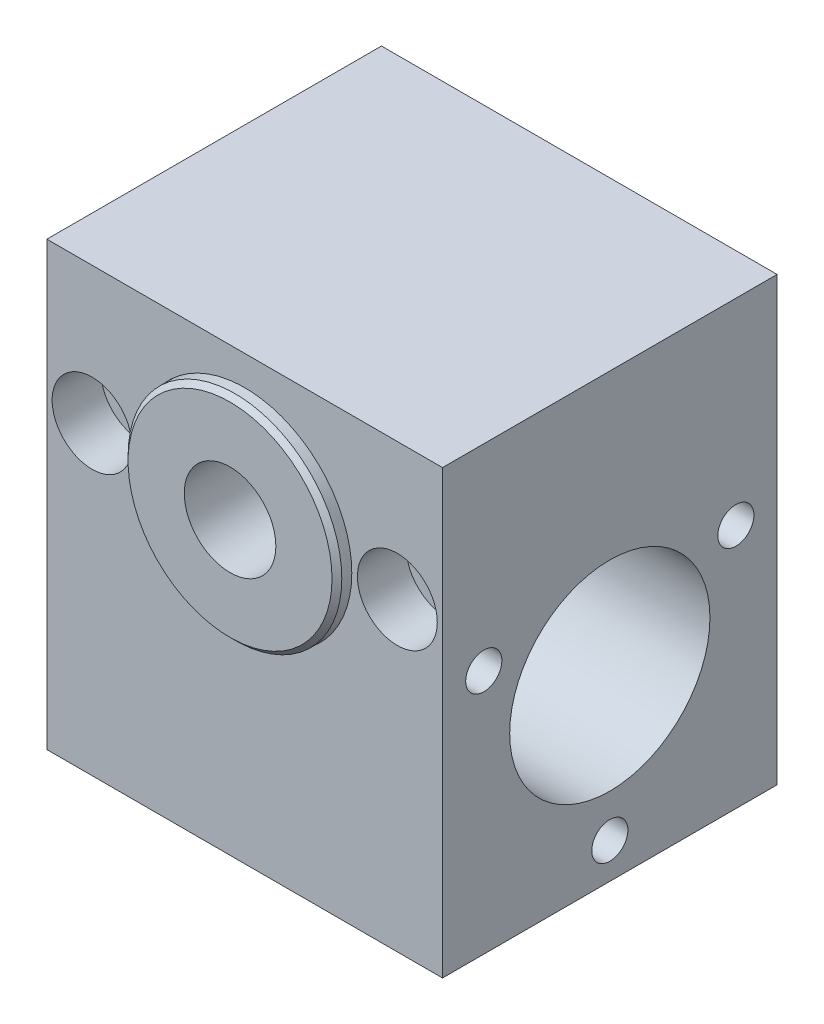
SolidWorks part; units mm, degrees
material "6061-T6 (SS)"
ref_plane "Front Plane" through (0, 0, 0) normal (0, 0, 1) x (1, 0, 0)
ref_plane "Top Plane" through (0, 0, 0) normal (0, 1, 0) x (1, 0, 0)
ref_plane "Right Plane" through (0, 0, 0) normal (1, 0, 0) x (0, 0, -1)
sketch "Sketch1" plane through (0, 0, 0) normal (1, 0, 0) x (0, 0, -1)
  line L0 (-17.399, 0) -> (17.399, 0)
  line L1 (17.399, 0) -> (17.399, 45.974)
  line L2 (17.399, 45.974) -> (-17.399, 45.974)
  line L3 (-17.399, 45.974) -> (-17.399, 0)
  circle A0 centre (0, 18.542) radius 10.414
extrude "Boss-Extrude1" add sketch "Sketch1" against normal blind 20.574 and the other way blind 20.574
ref_plane "Plane1" through (15.875, 0, 0) normal (1, 0, 0) x (0, 0, -1)
sketch "Sketch2" plane through (15.875, 0, 0) normal (1, 0, 0) x (0, 0, -1)
  line L0 (-17.399, 31.75) -> (-17.399, 35.9029)
  line L1 (-17.399, 35.9029) -> (-12.319, 35.9029)
  line L2 (-12.319, 35.9029) -> (-12.319, 34.3297)
  line L3 (-12.319, 34.3297) -> (12.319, 34.3297)
  line L4 (12.319, 34.3297) -> (12.319, 35.9029)
  line L5 (12.319, 35.9029) -> (17.399, 35.9029)
  line L6 (17.399, 35.9029) -> (17.399, 31.75)
  line L7 (17.399, 31.75) -> (-17.399, 31.75)
  line L8 (17.399, 31.75) -> (-17.399, 31.75) construction
revolve "Cut-Revolve1" cut sketch "Sketch2" angle 360 about L8 reverse direction yes
ref_plane "Plane2" through (-15.875, 0, 0) normal (1, 0, 0) x (0, 0, -1)
sketch "Sketch3" plane through (-15.875, 0, 0) normal (1, 0, 0) x (0, 0, -1)
  line L0 (-17.399, 31.75) -> (-17.399, 35.9029)
  line L1 (-17.399, 35.9029) -> (-12.319, 35.9029)
  line L2 (-12.319, 35.9029) -> (-12.319, 34.3297)
  line L3 (-12.319, 34.3297) -> (12.319, 34.3297)
  line L4 (12.319, 34.3297) -> (12.319, 35.9029)
  line L5 (12.319, 35.9029) -> (17.399, 35.9029)
  line L6 (17.399, 35.9029) -> (17.399, 31.75)
  line L7 (17.399, 31.75) -> (-17.399, 31.75)
  line L8 (17.399, 31.75) -> (-17.399, 31.75) construction
revolve "Cut-Revolve2" cut sketch "Sketch3" angle 360 about L8 reverse direction yes
ref_plane "Plane3" through (0, 0, 12.7) normal (0, 0, 1) x (1, 0, 0)
hole_wizard "Hole1" positions "Sketch5" profile "Sketch4" legacy
sketch "Sketch5" plane through (0, 0, 0) normal (0, -1, 0) x (-1, 0, 0)
  point P0 (0, -12.7)
sketch "Sketch4" plane through (0, 0, 12.7) normal (1, 0, 0) x (0, 0, -1)
  line L0 (0, 0) -> (0, 12.7277)
  line L1 (0, 12.7277) -> (1.9837, 11.5824)
  line L2 (1.9837, 11.5824) -> (1.9837, 0.4293)
  line L3 (1.9837, 0.4293) -> (2.413, 0)
  line L4 (2.413, 0) -> (0, 0)
  line L5 (0, -14.3089) -> (0, 102.4216) construction
  line L6 (0, 12.7277) -> (-1.9837, 11.5824) construction
  line L7 (-1.9837, 0.4293) -> (-2.413, 0) construction
  dimension "Diameter" = 3.9675
  dimension "Depth" = 11.5824
  dimension "C-Sink Diameter" = 4.826
  dimension "C-Sink Angle" = 90
  dimension "Drill Angle" = 120
cosmetic thread "Cosmetic Thread1" parameters "D1"=9.652, "D2"=4.826
ref_plane "Plane4" through (0, 0, -12.7) normal (0, 0, 1) x (1, 0, 0)
hole_wizard "Hole2" positions "Sketch7" profile "Sketch6" legacy
sketch "Sketch7" plane through (0, 0, 0) normal (0, -1, 0) x (-1, 0, 0)
  point P0 (0, 12.7)
sketch "Sketch6" plane through (0, 0, -12.7) normal (1, 0, 0) x (0, 0, -1)
  line L0 (0, 0) -> (0, 12.7277)
  line L1 (0, 12.7277) -> (1.9837, 11.5824)
  line L2 (1.9837, 11.5824) -> (1.9837, 0.4293)
  line L3 (1.9837, 0.4293) -> (2.413, 0)
  line L4 (2.413, 0) -> (0, 0)
  line L5 (0, -14.3089) -> (0, 102.4216) construction
  line L6 (0, 12.7277) -> (-1.9837, 11.5824) construction
  line L7 (-1.9837, 0.4293) -> (-2.413, 0) construction
  dimension "Diameter" = 3.9675
  dimension "Depth" = 11.5824
  dimension "C-Sink Diameter" = 4.826
  dimension "C-Sink Angle" = 90
  dimension "Drill Angle" = 120
cosmetic thread "Cosmetic Thread2" parameters "D1"=9.652, "D2"=4.826
hole_wizard "Hole3" positions "Sketch9" profile "Sketch8" legacy
sketch "Sketch9" plane through (0, 0, 17.399) normal (0, 0, 1) x (1, 0, 0)
  point P0 (0, 31.75)
sketch "Sketch8" plane through (0, 31.75, 17.399) normal (1, 0, 0) x (0, -1, 0)
  line L0 (0, 0) -> (0, 34.798)
  line L1 (0, 34.798) -> (4.7625, 34.798)
  line L2 (4.7625, 34.798) -> (4.7625, 24.638)
  line L3 (4.7625, 24.638) -> (11.1379, 24.638)
  line L4 (11.1379, 24.638) -> (11.1379, 0)
  line L5 (11.1379, 0) -> (0, 0)
  line L6 (0, 110) -> (0, -10) construction
  dimension "Diameter" = 9.525
  dimension "Depth" = 34.798
  dimension "C-Bore Diameter" = 22.2758
  dimension "C-Bore Depth" = 24.638
ref_plane "Plane5" through (20.574, 0, 0) normal (1, 0, 0) x (0, 0, -1)
ref_plane "Plane6" through (-20.574, 0, 0) normal (1, 0, 0) x (0, 0, -1)
ref_plane "Plane7" through (0, 0, 18.923) normal (0, 0, 1) x (1, 0, 0)
ref_plane "Plane8" through (0, 0, 44.323) normal (0, 0, 1) x (1, 0, 0)
ref_plane "Plane9" through (0, 0, -44.323) normal (0, 0, 1) x (1, 0, 0)
ref_plane "Plane10" through (0, 0, -17.399) normal (0, 0, 1) x (1, 0, 0)
ref_plane "Plane11" through (0, 0, -18.923) normal (0, 0, 1) x (1, 0, 0)
ref_plane "Plane12" through (0, 0, -17.399) normal (0, 0, 1) x (1, 0, 0)
sketch "Sketch10" plane through (0, 0, 0) normal (1, 0, 0) x (0, 0, -1)
  line L0 (-18.923, 42.3545) -> (-18.923, 36.5125)
  line L1 (-18.923, 36.5125) -> (7.239, 36.5125)
  line L2 (7.239, 36.5125) -> (7.239, 42.8625)
  line L3 (7.239, 42.8625) -> (-18.415, 42.8625)
  line L4 (-18.415, 42.8625) -> (-18.923, 42.3545)
  line L5 (7.239, 31.75) -> (-18.923, 31.75) construction
revolve "Revolve1" add sketch "Sketch10" angle 360 about L5 reverse direction yes
ref_plane "Plane13" through (20.574, 0, 0) normal (1, 0, 0) x (0, 0, -1)
hole_wizard "Hole4" positions "Sketch12" profile "Sketch11" legacy
sketch "Sketch12" plane through (20.574, 0, 0) normal (1, 0, 0) x (0, 0, -1)
  point P0 (13.1085, 25.5119)
sketch "Sketch11" plane through (20.574, 25.5119, -13.1085) normal (0, 1, 0) x (0, 0, -1)
  line L0 (0, 0) -> (0, 7.5184)
  line L1 (0, 7.5184) -> (1.8796, 7.5184)
  line L2 (1.8796, 7.5184) -> (1.8796, 0)
  line L3 (1.8796, 0) -> (0, 0)
  line L4 (0, 110) -> (0, -10) construction
  dimension "Diameter" = 3.7592
  dimension "Depth" = 7.5184
sketch "Sketch13" plane through (20.574, 0, 0) normal (1, 0, 0) x (0, 0, -1)
  line L0 (13.1085, 25.5119) -> (-13.1085, 25.5119)
  line L1 (13.1085, 25.5119) -> (0, 3.6957)
pattern_linear "LPattern2" count 2 spacing 26.217 along (0, 0, 1) count 2 spacing 25.4515 along (0, -0.8572, 0.515) skipping (1, 1) of "Hole4"
ref_plane "Plane14" through (-20.574, 0, 0) normal (1, 0, 0) x (0, 0, -1)
hole_wizard "Hole5" positions "Sketch15" profile "Sketch14" legacy
sketch "Sketch15" plane through (-20.574, 0, 0) normal (-1, 0, 0) x (0, 0, 1)
  point P0 (-13.1085, 25.5119)
sketch "Sketch14" plane through (-20.574, 25.5119, -13.1085) normal (0, 1, 0) x (0, 0, 1)
  line L0 (0, 0) -> (0, 7.5184)
  line L1 (0, 7.5184) -> (1.8796, 7.5184)
  line L2 (1.8796, 7.5184) -> (1.8796, 0)
  line L3 (1.8796, 0) -> (0, 0)
  line L4 (0, 110) -> (0, -10) construction
  dimension "Diameter" = 3.7592
  dimension "Depth" = 7.5184
sketch "Sketch16" plane through (-20.574, 0, 0) normal (1, 0, 0) x (0, 0, -1)
  line L0 (13.1085, 25.5119) -> (-13.1085, 25.5119)
  line L1 (13.1085, 25.5119) -> (0, 3.6957)
pattern_linear "LPattern4" count 2 spacing 26.217 along (0, 0, 1) count 2 spacing 25.4515 along (0, -0.8572, 0.515) skipping (1, 1) of "Hole5"
ref_plane "Plane15" through (0, 31.75, 0) normal (0, 1, 0) x (1, 0, 0)
ref_plane "a1 XY" through (0, 0, 0) normal (0, 0, 1) x (1, 0, 0)
ref_plane "a1 XZ" through (0, 45.974, 0) normal (0, -1, 0) x (-1, 0, 0)
ref_plane "a1 YZ" through (-20.574, 0, 0) normal (1, 0, 0) x (0, 0, -1)
ref_axis "a1 X" through (-80.9, 45.974, 0) along (1, 0, 0)
ref_axis "a1 Y" through (-20.574, -50, 0) along (0, 1, 0)
ref_axis "a1 Z" through (-20.574, 45.974, 80.9) along (0, 0, -1)
sketch3d "a1"
  point P0 (-20.574, 45.974, 0)
ref_plane "a2 XY" through (0, 0, 0) normal (0, 0, 1) x (1, 0, 0)
ref_plane "a2 XZ" through (0, 45.974, 0) normal (0, -1, 0) x (-1, 0, 0)
ref_plane "a2 YZ" through (20.574, 0, 0) normal (1, 0, 0) x (0, 0, -1)
ref_axis "a2 X" through (-80.9, 45.974, 0) along (1, 0, 0)
ref_axis "a2 Y" through (20.574, -50, 0) along (0, 1, 0)
ref_axis "a2 Z" through (20.574, 45.974, 80.9) along (0, 0, -1)
sketch3d "a2"
  point P0 (20.574, 45.974, 0)
ref_plane "ab XY" through (0, 0, 0) normal (1, 0, 0) x (0, 0, -1)
ref_plane "ab XZ" through (0, 18.542, 0) normal (0, -1, 0) x (-1, 0, 0)
ref_plane "ab YZ" through (0, 0, 0) normal (0, 0, -1) x (-1, 0, 0)
ref_axis "ab X" through (0, 18.542, 80.9) along (0, 0, -1)
ref_axis "ab Y" through (0, -50, 0) along (0, 1, 0)
ref_axis "ab Z" through (80.9, 18.542, 0) along (-1, 0, 0)
sketch3d "ab"
  point P0 (0, 18.542, 0)
ref_plane "b1 XY" through (0, 0, 0) normal (0, 0, 1) x (1, 0, 0)
ref_plane "b1 XZ" through (0, 31.75, 0) normal (0, -1, 0) x (-1, 0, 0)
ref_plane "b1 YZ" through (-15.875, 0, 0) normal (1, 0, 0) x (0, 0, -1)
ref_axis "b1 X" through (-80.9, 31.75, 0) along (1, 0, 0)
ref_axis "b1 Y" through (-15.875, -50, 0) along (0, 1, 0)
ref_axis "b1 Z" through (-15.875, 31.75, 80.9) along (0, 0, -1)
sketch3d "b1"
  point P0 (-15.875, 31.75, 0)
ref_plane "b2 XY" through (0, 0, 0) normal (0, 0, 1) x (1, 0, 0)
ref_plane "b2 XZ" through (0, 31.75, 0) normal (0, -1, 0) x (-1, 0, 0)
ref_plane "b2 YZ" through (15.875, 0, 0) normal (1, 0, 0) x (0, 0, -1)
ref_axis "b2 X" through (-80.9, 31.75, 0) along (1, 0, 0)
ref_axis "b2 Y" through (15.875, -50, 0) along (0, 1, 0)
ref_axis "b2 Z" through (15.875, 31.75, 80.9) along (0, 0, -1)
sketch3d "b2"
  point P0 (15.875, 31.75, 0)
ref_plane "body a single XY" through (-20.574, 0, 0) normal (1, 0, 0) x (0, 0, -1)
ref_plane "body a single XZ" through (0, 18.542, 0) normal (0, -1, 0) x (-1, 0, 0)
ref_plane "body a single YZ" through (0, 0, 0) normal (0, 0, -1) x (-1, 0, 0)
ref_axis "body a single X" through (-20.574, 18.542, 80.9) along (0, 0, -1)
ref_axis "body a single Y" through (-20.574, -50, 0) along (0, 1, 0)
ref_axis "body a single Z" through (80.9, 18.542, 0) along (-1, 0, 0)
sketch3d "body a single"
  point P0 (-20.574, 18.542, 0)
ref_plane "body b single XY" through (20.574, 0, 0) normal (1, 0, 0) x (0, 0, -1)
ref_plane "body b single XZ" through (0, 18.542, 0) normal (0, -1, 0) x (-1, 0, 0)
ref_plane "body b single YZ" through (0, 0, 0) normal (0, 0, -1) x (-1, 0, 0)
ref_axis "body b single X" through (20.574, 18.542, 80.9) along (0, 0, -1)
ref_axis "body b single Y" through (20.574, -50, 0) along (0, 1, 0)
ref_axis "body b single Z" through (80.9, 18.542, 0) along (-1, 0, 0)
sketch3d "body b single"
  point P0 (20.574, 18.542, 0)
ref_plane "c1 XY" through (0, 0, 0) normal (0, 0, 1) x (1, 0, 0)
ref_plane "c1 XZ" through (0, 31.75, 0) normal (0, -1, 0) x (-1, 0, 0)
ref_plane "c1 YZ" through (-15.875, 0, 0) normal (1, 0, 0) x (0, 0, -1)
ref_axis "c1 X" through (-80.9, 31.75, 0) along (1, 0, 0)
ref_axis "c1 Y" through (-15.875, -50, 0) along (0, 1, 0)
ref_axis "c1 Z" through (-15.875, 31.75, 80.9) along (0, 0, -1)
sketch3d "c1"
  point P0 (-15.875, 31.75, 0)
ref_plane "c2 XY" through (0, 0, 0) normal (0, 0, 1) x (1, 0, 0)
ref_plane "c2 XZ" through (0, 31.75, 0) normal (0, -1, 0) x (-1, 0, 0)
ref_plane "c2 YZ" through (0, 0, 0) normal (1, 0, 0) x (0, 0, -1)
ref_axis "c2 X" through (-80.9, 31.75, 0) along (1, 0, 0)
ref_axis "c2 Y" through (0, -50, 0) along (0, 1, 0)
ref_axis "c2 Z" through (0, 31.75, 80.9) along (0, 0, -1)
sketch3d "c2"
  point P0 (0, 31.75, 0)
ref_plane "e1 XY" through (0, 0, 0) normal (1, 0, 0) x (0, 0, -1)
ref_plane "e1 XZ" through (0, 45.974, 0) normal (0, -1, 0) x (-1, 0, 0)
ref_plane "e1 YZ" through (0, 0, 17.399) normal (0, 0, -1) x (-1, 0, 0)
ref_axis "e1 X" through (0, 45.974, 80.9) along (0, 0, -1)
ref_axis "e1 Y" through (0, -50, 17.399) along (0, 1, 0)
ref_axis "e1 Z" through (80.9, 45.974, 17.399) along (-1, 0, 0)
sketch3d "e1"
  point P0 (0, 45.974, 17.399)
ref_plane "e2 XY" through (0, 0, 0) normal (1, 0, 0) x (0, 0, -1)
ref_plane "e2 XZ" through (0, 0, 0) normal (0, -1, 0) x (-1, 0, 0)
ref_plane "e2 YZ" through (0, 0, 17.399) normal (0, 0, -1) x (-1, 0, 0)
ref_axis "e2 X" through (0, 0, 80.9) along (0, 0, -1)
ref_axis "e2 Y" through (0, -50, 17.399) along (0, 1, 0)
ref_axis "e2 Z" through (80.9, 0, 17.399) along (-1, 0, 0)
sketch3d "e2"
  point P0 (0, 0, 17.399)
ref_plane "f1 XY" through (0, 0, 0) normal (0, 0, 1) x (1, 0, 0)
ref_plane "f1 XZ" through (0, 31.75, 0) normal (0, -1, 0) x (-1, 0, 0)
ref_plane "f1 YZ" through (13.2953, 0, 0) normal (1, 0, 0) x (0, 0, -1)
ref_axis "f1 X" through (-80.9, 31.75, 0) along (1, 0, 0)
ref_axis "f1 Y" through (13.2953, -50, 0) along (0, 1, 0)
ref_axis "f1 Z" through (13.2953, 31.75, 80.9) along (0, 0, -1)
sketch3d "f1"
  point P0 (13.2953, 31.75, 0)
ref_plane "f2 XY" through (0, 0, 0) normal (0, 0, 1) x (1, 0, 0)
ref_plane "f2 XZ" through (0, 31.75, 0) normal (0, -1, 0) x (-1, 0, 0)
ref_plane "f2 YZ" through (18.4547, 0, 0) normal (1, 0, 0) x (0, 0, -1)
ref_axis "f2 X" through (-80.9, 31.75, 0) along (1, 0, 0)
ref_axis "f2 Y" through (18.4547, -50, 0) along (0, 1, 0)
ref_axis "f2 Z" through (18.4547, 31.75, 80.9) along (0, 0, -1)
sketch3d "f2"
  point P0 (18.4547, 31.75, 0)
ref_plane "g1 XY" through (0, 0, 0) normal (0, 0, 1) x (1, 0, 0)
ref_plane "g1 XZ" through (0, 31.75, 0) normal (0, -1, 0) x (-1, 0, 0)
ref_plane "g1 YZ" through (-11.1125, 0, 0) normal (1, 0, 0) x (0, 0, -1)
ref_axis "g1 X" through (-80.9, 31.75, 0) along (1, 0, 0)
ref_axis "g1 Y" through (-11.1125, -50, 0) along (0, 1, 0)
ref_axis "g1 Z" through (-11.1125, 31.75, 80.9) along (0, 0, -1)
sketch3d "g1"
  point P0 (-11.1125, 31.75, 0)
ref_plane "g1_1 XY" through (0, 31.75, 0) normal (0, 1, 0) x (1, 0, 0)
ref_plane "g1_1 XZ" through (0, 0, 17.399) normal (0, 0, 1) x (1, 0, 0)
ref_plane "g1_1 YZ" through (-11.1125, 0, 0) normal (1, 0, 0) x (0, 0, -1)
ref_axis "g1_1 X" through (-80.9, 31.75, 17.399) along (1, 0, 0)
ref_axis "g1_1 Y" through (-11.1125, 31.75, 50) along (0, 0, -1)
ref_axis "g1_1 Z" through (-11.1125, 50, 17.399) along (0, -1, 0)
sketch3d "g1_1"
  point P0 (-11.1125, 31.75, 17.399)
ref_plane "g1_2 XY" through (0, 31.75, 0) normal (0, 1, 0) x (1, 0, 0)
ref_plane "g1_2 XZ" through (0, 0, 17.399) normal (0, 0, 1) x (1, 0, 0)
ref_plane "g1_2 YZ" through (11.1125, 0, 0) normal (1, 0, 0) x (0, 0, -1)
ref_axis "g1_2 X" through (-80.9, 31.75, 17.399) along (1, 0, 0)
ref_axis "g1_2 Y" through (11.1125, 31.75, 50) along (0, 0, -1)
ref_axis "g1_2 Z" through (11.1125, 50, 17.399) along (0, -1, 0)
sketch3d "g1_2"
  point P0 (11.1125, 31.75, 17.399)
ref_plane "g2 XY" through (0, 0, 0) normal (0, 0, 1) x (1, 0, 0)
ref_plane "g2 XZ" through (0, 31.75, 0) normal (0, -1, 0) x (-1, 0, 0)
ref_plane "g2 YZ" through (11.1125, 0, 0) normal (1, 0, 0) x (0, 0, -1)
ref_axis "g2 X" through (-80.9, 31.75, 0) along (1, 0, 0)
ref_axis "g2 Y" through (11.1125, -50, 0) along (0, 1, 0)
ref_axis "g2 Z" through (11.1125, 31.75, 80.9) along (0, 0, -1)
sketch3d "g2"
  point P0 (11.1125, 31.75, 0)
ref_plane "h1 XY" through (0, 0, 0) normal (1, 0, 0) x (0, 0, -1)
ref_plane "h1 XZ" through (0, 36.5125, 0) normal (0, -1, 0) x (-1, 0, 0)
ref_plane "h1 YZ" through (0, 0, 44.323) normal (0, 0, -1) x (-1, 0, 0)
ref_axis "h1 X" through (0, 36.5125, 80.9) along (0, 0, -1)
ref_axis "h1 Y" through (0, -50, 44.323) along (0, 1, 0)
ref_axis "h1 Z" through (80.9, 36.5125, 44.323) along (-1, 0, 0)
sketch3d "h1"
  point P0 (0, 36.5125, 44.323)
ref_plane "h2 XY" through (0, 0, 0) normal (1, 0, 0) x (0, 0, -1)
ref_plane "h2 XZ" through (0, 26.9875, 0) normal (0, -1, 0) x (-1, 0, 0)
ref_plane "h2 YZ" through (0, 0, 44.323) normal (0, 0, -1) x (-1, 0, 0)
ref_axis "h2 X" through (0, 26.9875, 80.9) along (0, 0, -1)
ref_axis "h2 Y" through (0, -50, 44.323) along (0, 1, 0)
ref_axis "h2 Z" through (80.9, 26.9875, 44.323) along (-1, 0, 0)
sketch3d "h2"
  point P0 (0, 26.9875, 44.323)
ref_plane "l_ab XY" through (0, 0, 0) normal (0, 0, 1) x (1, 0, 0)
ref_plane "l_ab XZ" through (0, 0, 0) normal (0, -1, 0) x (-1, 0, 0)
ref_plane "l_ab YZ" through (0, 0, 0) normal (1, 0, 0) x (0, 0, -1)
ref_axis "l_ab X" through (-80.9, 0, 0) along (1, 0, 0)
ref_axis "l_ab Y" through (0, -50, 0) along (0, 1, 0)
ref_axis "l_ab Z" through (0, 0, 80.9) along (0, 0, -1)
sketch3d "l_ab"
  point P0 (0, 0, 0)
ref_plane "l_cd XY" through (0, 0, 0) normal (0, 0, 1) x (1, 0, 0)
ref_plane "l_cd XZ" through (0, 45.974, 0) normal (0, -1, 0) x (-1, 0, 0)
ref_plane "l_cd YZ" through (0, 0, 0) normal (1, 0, 0) x (0, 0, -1)
ref_axis "l_cd X" through (-80.9, 45.974, 0) along (1, 0, 0)
ref_axis "l_cd Y" through (0, -50, 0) along (0, 1, 0)
ref_axis "l_cd Z" through (0, 45.974, 80.9) along (0, 0, -1)
sketch3d "l_cd"
  point P0 (0, 45.974, 0)
ref_plane "m1 XY" through (0, 0, 0) normal (1, 0, 0) x (0, 0, -1)
ref_plane "m1 XZ" through (0, 45.974, 0) normal (0, -1, 0) x (-1, 0, 0)
ref_plane "m1 YZ" through (0, 0, 17.399) normal (0, 0, -1) x (-1, 0, 0)
ref_axis "m1 X" through (0, 45.974, 80.9) along (0, 0, -1)
ref_axis "m1 Y" through (0, -50, 17.399) along (0, 1, 0)
ref_axis "m1 Z" through (80.9, 45.974, 17.399) along (-1, 0, 0)
sketch3d "m1"
  point P0 (0, 45.974, 17.399)
ref_plane "m2 XY" through (0, 0, 0) normal (1, 0, 0) x (0, 0, -1)
ref_plane "m2 XZ" through (0, 45.974, 0) normal (0, -1, 0) x (-1, 0, 0)
ref_plane "m2 YZ" through (0, 0, -17.399) normal (0, 0, -1) x (-1, 0, 0)
ref_axis "m2 X" through (0, 45.974, 80.9) along (0, 0, -1)
ref_axis "m2 Y" through (0, -50, -17.399) along (0, 1, 0)
ref_axis "m2 Z" through (80.9, 45.974, -17.399) along (-1, 0, 0)
sketch3d "m2"
  point P0 (0, 45.974, -17.399)
ref_plane "n1 XY" through (0, 0, 0) normal (1, 0, 0) x (0, 0, -1)
ref_plane "n1 XZ" through (0, 31.75, 0) normal (0, -1, 0) x (-1, 0, 0)
ref_plane "n1 YZ" through (0, 0, 44.323) normal (0, 0, -1) x (-1, 0, 0)
ref_axis "n1 X" through (0, 31.75, 80.9) along (0, 0, -1)
ref_axis "n1 Y" through (0, -50, 44.323) along (0, 1, 0)
ref_axis "n1 Z" through (80.9, 31.75, 44.323) along (-1, 0, 0)
sketch3d "n1"
  point P0 (0, 31.75, 44.323)
ref_plane "n2 XY" through (0, 0, 0) normal (1, 0, 0) x (0, 0, -1)
ref_plane "n2 XZ" through (0, 45.974, 0) normal (0, -1, 0) x (-1, 0, 0)
ref_plane "n2 YZ" through (0, 0, 17.399) normal (0, 0, -1) x (-1, 0, 0)
ref_axis "n2 X" through (0, 45.974, 80.9) along (0, 0, -1)
ref_axis "n2 Y" through (0, -50, 17.399) along (0, 1, 0)
ref_axis "n2 Z" through (80.9, 45.974, 17.399) along (-1, 0, 0)
sketch3d "n2"
  point P0 (0, 45.974, 17.399)
ref_plane "o1 XY" through (0, 0, 0) normal (1, 0, 0) x (0, 0, -1)
ref_plane "o1 XZ" through (0, 45.974, 0) normal (0, -1, 0) x (-1, 0, 0)
ref_plane "o1 YZ" through (0, 0, 17.399) normal (0, 0, -1) x (-1, 0, 0)
ref_axis "o1 X" through (0, 45.974, 80.9) along (0, 0, -1)
ref_axis "o1 Y" through (0, -50, 17.399) along (0, 1, 0)
ref_axis "o1 Z" through (80.9, 45.974, 17.399) along (-1, 0, 0)
sketch3d "o1"
  point P0 (0, 45.974, 17.399)
ref_plane "o2 XY" through (0, 0, 0) normal (1, 0, 0) x (0, 0, -1)
ref_plane "o2 XZ" through (0, 45.974, 0) normal (0, -1, 0) x (-1, 0, 0)
ref_plane "o2 YZ" through (0, 0, 0) normal (0, 0, -1) x (-1, 0, 0)
ref_axis "o2 X" through (0, 45.974, 80.9) along (0, 0, -1)
ref_axis "o2 Y" through (0, -50, 0) along (0, 1, 0)
ref_axis "o2 Z" through (80.9, 45.974, 0) along (-1, 0, 0)
sketch3d "o2"
  point P0 (0, 45.974, 0)
ref_plane "p1 XY" through (0, 0, 0) normal (1, 0, 0) x (0, 0, -1)
ref_plane "p1 XZ" through (0, 31.75, 0) normal (0, -1, 0) x (-1, 0, 0)
ref_plane "p1 YZ" through (0, 0, 18.923) normal (0, 0, -1) x (-1, 0, 0)
ref_axis "p1 X" through (0, 31.75, 80.9) along (0, 0, -1)
ref_axis "p1 Y" through (0, -50, 18.923) along (0, 1, 0)
ref_axis "p1 Z" through (80.9, 31.75, 18.923) along (-1, 0, 0)
sketch3d "p1"
  point P0 (0, 31.75, 18.923)
ref_plane "p2 XY" through (0, 0, 0) normal (1, 0, 0) x (0, 0, -1)
ref_plane "p2 XZ" through (0, 45.974, 0) normal (0, -1, 0) x (-1, 0, 0)
ref_plane "p2 YZ" through (0, 0, 17.399) normal (0, 0, -1) x (-1, 0, 0)
ref_axis "p2 X" through (0, 45.974, 80.9) along (0, 0, -1)
ref_axis "p2 Y" through (0, -50, 17.399) along (0, 1, 0)
ref_axis "p2 Z" through (80.9, 45.974, 17.399) along (-1, 0, 0)
sketch3d "p2"
  point P0 (0, 45.974, 17.399)
ref_plane "piston single XY" through (0, 0, 0) normal (1, 0, 0) x (0, 0, -1)
ref_plane "piston single XZ" through (0, 18.542, 0) normal (0, -1, 0) x (-1, 0, 0)
ref_plane "piston single YZ" through (0, 0, 0) normal (0, 0, -1) x (-1, 0, 0)
ref_axis "piston single X" through (0, 18.542, 80.9) along (0, 0, -1)
ref_axis "piston single Y" through (0, -50, 0) along (0, 1, 0)
ref_axis "piston single Z" through (80.9, 18.542, 0) along (-1, 0, 0)
sketch3d "piston single"
  point P0 (0, 18.542, 0)
ref_plane "q1 XY" through (0, 0, 0) normal (1, 0, 0) x (0, 0, -1)
ref_plane "q1 XZ" through (0, 31.75, 0) normal (0, -1, 0) x (-1, 0, 0)
ref_plane "q1 YZ" through (0, 0, 44.323) normal (0, 0, -1) x (-1, 0, 0)
ref_axis "q1 X" through (0, 31.75, 80.9) along (0, 0, -1)
ref_axis "q1 Y" through (0, -50, 44.323) along (0, 1, 0)
ref_axis "q1 Z" through (80.9, 31.75, 44.323) along (-1, 0, 0)
sketch3d "q1"
  point P0 (0, 31.75, 44.323)
ref_plane "q2 XY" through (0, 0, 0) normal (1, 0, 0) x (0, 0, -1)
ref_plane "q2 XZ" through (0, 31.75, 0) normal (0, -1, 0) x (-1, 0, 0)
ref_plane "q2 YZ" through (0, 0, 31.623) normal (0, 0, -1) x (-1, 0, 0)
ref_axis "q2 X" through (0, 31.75, 80.9) along (0, 0, -1)
ref_axis "q2 Y" through (0, -50, 31.623) along (0, 1, 0)
ref_axis "q2 Z" through (80.9, 31.75, 31.623) along (-1, 0, 0)
sketch3d "q2"
  point P0 (0, 31.75, 31.623)
ref_plane "s1 XY" through (0, 0, 0) normal (1, 0, 0) x (0, 0, -1)
ref_plane "s1 XZ" through (0, 31.75, 0) normal (0, -1, 0) x (-1, 0, 0)
ref_plane "s1 YZ" through (0, 0, 17.399) normal (0, 0, -1) x (-1, 0, 0)
ref_axis "s1 X" through (0, 31.75, 80.9) along (0, 0, -1)
ref_axis "s1 Y" through (0, -50, 17.399) along (0, 1, 0)
ref_axis "s1 Z" through (80.9, 31.75, 17.399) along (-1, 0, 0)
sketch3d "s1"
  point P0 (0, 31.75, 17.399)
ref_plane "s2 XY" through (0, 0, 0) normal (1, 0, 0) x (0, 0, -1)
ref_plane "s2 XZ" through (0, 0, 0) normal (0, -1, 0) x (-1, 0, 0)
ref_plane "s2 YZ" through (0, 0, 17.399) normal (0, 0, -1) x (-1, 0, 0)
ref_axis "s2 X" through (0, 0, 80.9) along (0, 0, -1)
ref_axis "s2 Y" through (0, -50, 17.399) along (0, 1, 0)
ref_axis "s2 Z" through (80.9, 0, 17.399) along (-1, 0, 0)
sketch3d "s2"
  point P0 (0, 0, 17.399)
ref_plane "t1 XY" through (0, 0, 0) normal (1, 0, 0) x (0, 0, -1)
ref_plane "t1 XZ" through (0, 18.542, 0) normal (0, -1, 0) x (-1, 0, 0)
ref_plane "t1 YZ" through (0, 0, 0) normal (0, 0, -1) x (-1, 0, 0)
ref_axis "t1 X" through (0, 18.542, 80.9) along (0, 0, -1)
ref_axis "t1 Y" through (0, -50, 0) along (0, 1, 0)
ref_axis "t1 Z" through (80.9, 18.542, 0) along (-1, 0, 0)
sketch3d "t1"
  point P0 (0, 18.542, 0)
ref_plane "t2 XY" through (0, 0, 0) normal (1, 0, 0) x (0, 0, -1)
ref_plane "t2 XZ" through (0, 0, 0) normal (0, -1, 0) x (-1, 0, 0)
ref_plane "t2 YZ" through (0, 0, 0) normal (0, 0, -1) x (-1, 0, 0)
ref_axis "t2 X" through (0, 0, 80.9) along (0, 0, -1)
ref_axis "t2 Y" through (0, -50, 0) along (0, 1, 0)
ref_axis "t2 Z" through (80.9, 0, 0) along (-1, 0, 0)
sketch3d "t2"
  point P0 (0, 0, 0)
ref_plane "to bearing XY" through (0, 0, 18.923) normal (0, 0, 1) x (1, 0, 0)
ref_plane "to bearing XZ" through (0, 31.75, 0) normal (0, -1, 0) x (-1, 0, 0)
ref_plane "to bearing YZ" through (0, 0, 0) normal (1, 0, 0) x (0, 0, -1)
ref_axis "to bearing X" through (-80.9, 31.75, 18.923) along (1, 0, 0)
ref_axis "to bearing Y" through (0, -50, 18.923) along (0, 1, 0)
ref_axis "to bearing Z" through (0, 31.75, 80.9) along (0, 0, -1)
sketch3d "to bearing"
  point P0 (0, 31.75, 18.923)
ref_plane "to bearing1 XY" through (0, 0, -18.923) normal (0, 0, 1) x (1, 0, 0)
ref_plane "to bearing1 XZ" through (0, 31.75, 0) normal (0, -1, 0) x (-1, 0, 0)
ref_plane "to bearing1 YZ" through (0, 0, 0) normal (1, 0, 0) x (0, 0, -1)
ref_axis "to bearing1 X" through (-80.9, 31.75, -18.923) along (1, 0, 0)
ref_axis "to bearing1 Y" through (0, -50, -18.923) along (0, 1, 0)
ref_axis "to bearing1 Z" through (0, 31.75, 80.9) along (0, 0, -1)
sketch3d "to bearing1"
  point P0 (0, 31.75, -18.923)
ref_plane "to cover plate XY" through (0, 0, -17.399) normal (0, 0, 1) x (1, 0, 0)
ref_plane "to cover plate XZ" through (0, 31.75, 0) normal (0, -1, 0) x (-1, 0, 0)
ref_plane "to cover plate YZ" through (0, 0, 0) normal (1, 0, 0) x (0, 0, -1)
ref_axis "to cover plate X" through (-80.9, 31.75, -17.399) along (1, 0, 0)
ref_axis "to cover plate Y" through (0, -50, -17.399) along (0, 1, 0)
ref_axis "to cover plate Z" through (0, 31.75, 80.9) along (0, 0, -1)
sketch3d "to cover plate"
  point P0 (0, 31.75, -17.399)
ref_plane "to shaft XY" through (0, 0, 44.323) normal (0, 0, 1) x (1, 0, 0)
ref_plane "to shaft XZ" through (0, 31.75, 0) normal (0, -1, 0) x (-1, 0, 0)
ref_plane "to shaft YZ" through (0, 0, 0) normal (1, 0, 0) x (0, 0, -1)
ref_axis "to shaft X" through (-80.9, 31.75, 44.323) along (1, 0, 0)
ref_axis "to shaft Y" through (0, -50, 44.323) along (0, 1, 0)
ref_axis "to shaft Z" through (0, 31.75, 80.9) along (0, 0, -1)
sketch3d "to shaft"
  point P0 (0, 31.75, 44.323)
ref_plane "to shaft E XY" through (0, 0, -44.323) normal (0, 0, 1) x (1, 0, 0)
ref_plane "to shaft E XZ" through (0, 31.75, 0) normal (0, -1, 0) x (-1, 0, 0)
ref_plane "to shaft E YZ" through (0, 0, 0) normal (1, 0, 0) x (0, 0, -1)
ref_axis "to shaft E X" through (-80.9, 31.75, -44.323) along (1, 0, 0)
ref_axis "to shaft E Y" through (0, -50, -44.323) along (0, 1, 0)
ref_axis "to shaft E Z" through (0, 31.75, 80.9) along (0, 0, -1)
sketch3d "to shaft E"
  point P0 (0, 31.75, -44.323)
ref_plane "w1 XY" through (0, 0, 0) normal (1, 0, 0) x (0, 0, -1)
ref_plane "w1 XZ" through (0, 0, 0) normal (0, -1, 0) x (-1, 0, 0)
ref_plane "w1 YZ" through (0, 0, 17.399) normal (0, 0, -1) x (-1, 0, 0)
ref_axis "w1 X" through (0, 0, 80.9) along (0, 0, -1)
ref_axis "w1 Y" through (0, -50, 17.399) along (0, 1, 0)
ref_axis "w1 Z" through (80.9, 0, 17.399) along (-1, 0, 0)
sketch3d "w1"
  point P0 (0, 0, 17.399)
ref_plane "w2 XY" through (0, 0, 0) normal (1, 0, 0) x (0, 0, -1)
ref_plane "w2 XZ" through (0, 0, 0) normal (0, -1, 0) x (-1, 0, 0)
ref_plane "w2 YZ" through (0, 0, 12.573) normal (0, 0, -1) x (-1, 0, 0)
ref_axis "w2 X" through (0, 0, 80.9) along (0, 0, -1)
ref_axis "w2 Y" through (0, -50, 12.573) along (0, 1, 0)
ref_axis "w2 Z" through (80.9, 0, 12.573) along (-1, 0, 0)
sketch3d "w2"
  point P0 (0, 0, 12.573)
ref_plane "x1 XY" through (0, 0, 0) normal (1, 0, 0) x (0, 0, -1)
ref_plane "x1 XZ" through (0, 0, 0) normal (0, -1, 0) x (-1, 0, 0)
ref_plane "x1 YZ" through (0, 0, 12.573) normal (0, 0, -1) x (-1, 0, 0)
ref_axis "x1 X" through (0, 0, 80.9) along (0, 0, -1)
ref_axis "x1 Y" through (0, -50, 12.573) along (0, 1, 0)
ref_axis "x1 Z" through (80.9, 0, 12.573) along (-1, 0, 0)
sketch3d "x1"
  point P0 (0, 0, 12.573)
ref_plane "x2 XY" through (0, 0, 0) normal (1, 0, 0) x (0, 0, -1)
ref_plane "x2 XZ" through (0, 0, 0) normal (0, -1, 0) x (-1, 0, 0)
ref_plane "x2 YZ" through (0, 0, -12.827) normal (0, 0, -1) x (-1, 0, 0)
ref_axis "x2 X" through (0, 0, 80.9) along (0, 0, -1)
ref_axis "x2 Y" through (0, -50, -12.827) along (0, 1, 0)
ref_axis "x2 Z" through (80.9, 0, -12.827) along (-1, 0, 0)
sketch3d "x2"
  point P0 (0, 0, -12.827)
